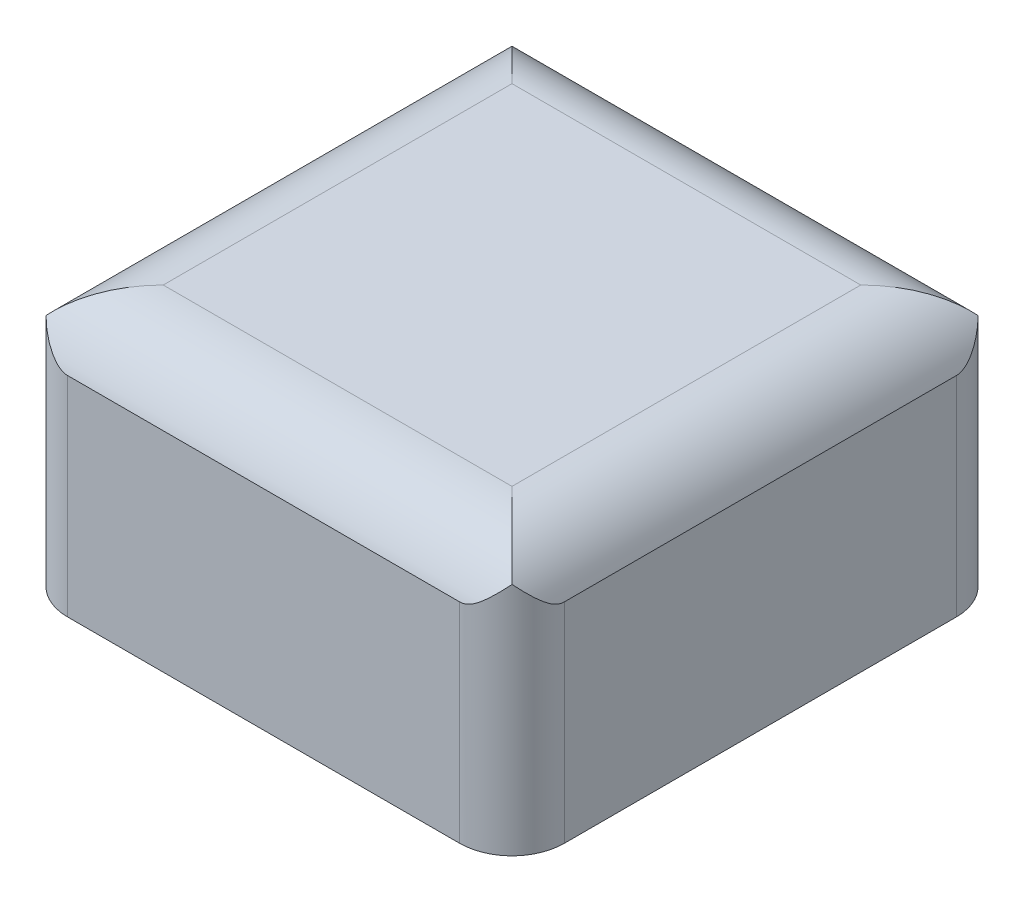
SolidWorks part; units mm, degrees
ref_plane "Front Plane" through (0, 0, 0) normal (0, 0, 1) x (1, 0, 0)
ref_plane "Top Plane" through (0, 0, 0) normal (0, 1, 0) x (1, 0, 0)
ref_plane "Right Plane" through (0, 0, 0) normal (1, 0, 0) x (0, 0, -1)
sketch "Sketch1" plane through (0, 0, 0) normal (0, 1, 0) x (1, 0, 0)
  line L1 (-2.5, 2.25) -> (2.5, 2.25)
  line L2 (-2.5, 2.25) -> (-2.5, -2.25)
  line L3 (-2.5, -2.25) -> (2.5, -2.25)
  line L4 (2.5, 2.25) -> (2.5, -2.25)
  line L5 (-2.5, 2.25) -> (2.5, -2.25) construction
  line L6 (-2.5, -2.25) -> (2.5, 2.25) construction
  line L7 (-0.7225, 2.065) -> (0.7225, 2.065)
  line L8 (-0.7225, 2.065) -> (-0.7225, -2.065)
  line L9 (-0.7225, -2.065) -> (0.7225, -2.065)
  line L10 (0.7225, 2.065) -> (0.7225, -2.065)
  line L11 (-0.7225, 2.065) -> (0.7225, -2.065) construction
  line L12 (-0.7225, -2.065) -> (0.7225, 2.065) construction
  line L13 (-2.065, 0.7225) -> (2.065, 0.7225)
  line L14 (-2.065, 0.7225) -> (-2.065, -0.7225)
  line L15 (-2.065, -0.7225) -> (2.065, -0.7225)
  line L16 (2.065, 0.7225) -> (2.065, -0.7225)
  line L17 (-2.065, 0.7225) -> (2.065, -0.7225) construction
  line L18 (-2.065, -0.7225) -> (2.065, 0.7225) construction
  point P0 (0, 0)
  point P6 (0, 0)
  point P11 (0, 0)
  dimension "D1" = 5
  dimension "D2" = 4.5
  dimension "D3" = 1.445
  dimension "D4" = 4.13
  dimension "D5" = 1.445
  dimension "D6" = 4.13
extrude "Boss-Extrude1" add sketch "Sketch1" along normal blind 4 contours L4 L1 L2 L3 L13 L16 L15 L10 L9 L8 L14 L7
sketch "Sketch2" plane through (0, 4, 0) normal (0, 1, 0) x (1, 0, 0)
  line L1 (-2.5, 2.25) -> (2.5, 2.25)
  line L2 (-2.5, 2.25) -> (-2.5, -2.25)
  line L3 (-2.5, -2.25) -> (2.5, -2.25)
  line L4 (2.5, 2.25) -> (2.5, -2.25)
  line L5 (-2.5, 2.25) -> (2.5, -2.25) construction
  line L6 (-2.5, -2.25) -> (2.5, 2.25) construction
  point P0 (0, 0)
extrude "Boss-Extrude2" add sketch "Sketch2" along normal blind 2
sketch "Sketch3" plane through (0, 6, 0) normal (0, 1, 0) x (1, 0, 0)
  line L1 (-9.5, 9.5) -> (9.5, 9.5)
  line L2 (-9.5, 9.5) -> (-9.5, -9.5)
  line L3 (-9.5, -9.5) -> (9.5, -9.5)
  line L4 (9.5, 9.5) -> (9.5, -9.5)
  line L5 (-9.5, 9.5) -> (9.5, -9.5) construction
  line L6 (-9.5, -9.5) -> (9.5, 9.5) construction
  point P0 (0, 0)
  dimension "D1" = 19
  dimension "D2" = 19
extrude "Boss-Extrude3" add sketch "Sketch3" along normal blind 2
fillet "Fillet1" radius 3 4 edges at (0, 8, 9.5) (-9.5, 8, 0) (0, 8, -9.5) (9.5, 8, 0)
sketch "Sketch4" plane through (0, 6, 0) normal (0, -1, 0) x (1, 0, 0)
  line L1 (-9.5, 9.5) -> (-8, 9.5)
  line L2 (-9.5, 9.5) -> (-9.5, 8)
  line L3 (-9.5, 8) -> (-8, 8)
  line L4 (-8, 9.5) -> (-8, 8)
  line L5 (-9.5, 9.5) -> (-8, 8) construction
  line L6 (-9.5, 8) -> (-8, 9.5) construction
  line L7 (9.5, -9.5) -> (8, -9.5)
  line L8 (9.5, -9.5) -> (9.5, -8)
  line L9 (9.5, -8) -> (8, -8)
  line L10 (8, -9.5) -> (8, -8)
  line L11 (9.5, -9.5) -> (8, -8) construction
  line L12 (9.5, -8) -> (8, -9.5) construction
  line L13 (-9.5, 9.5) -> (9.5, 9.5)
  line L14 (-9.5, 9.5) -> (-9.5, -9.5)
  line L15 (-9.5, -9.5) -> (9.5, -9.5)
  line L16 (9.5, 9.5) -> (9.5, -9.5)
  line L17 (-9.5, 9.5) -> (9.5, -9.5) construction
  line L18 (-9.5, -9.5) -> (9.5, 9.5) construction
  line L19 (8, -8) -> (-8, -8)
  line L20 (8, -8) -> (8, 8)
  line L21 (8, 8) -> (-8, 8)
  line L22 (-8, -8) -> (-8, 8)
  line L23 (8, -8) -> (-8, 8) construction
  line L24 (8, 8) -> (-8, -8) construction
  point P4 (-8.75, 8.75)
  point P10 (8.75, -8.75)
  point P12 (0, 0)
  point P13 (0, 0)
  line M9 (9.5, -9.5) -> (9.5, 9.5)
  line M10 (9.5, 9.5) -> (-9.5, 9.5)
  line M11 (-9.5, 9.5) -> (-9.5, -9.5)
  line M12 (-9.5, -9.5) -> (9.5, -9.5)
  dimension "D1" = 1.5
  dimension "D2" = 1.5
  dimension "D3" = 1.5
extrude "Boss-Extrude4" add sketch "Sketch4" along normal blind 8 contours L19 L22 L3 L10 M11 M12 | L21 L20 L9 L4 M9 M10 | L10 L9 M12 M9 | L4 L3 M10 M11
fillet "Fillet3" radius 3 4 edges at (0, 6, -2.25) (-2.5, 6, 0) (0, 6, 2.25) (2.5, 6, 0)
fillet "Fillet4" radius 1 8 edges at (3.3787, 5.1213, 3.1287) (-3.3787, 5.1213, 3.1287) (-3.3787, 5.1213, -3.1287) (3.3787, 5.1213, -3.1287) (2.5, 1.5, 2.25) (-2.5, 1.5, 2.25) (-2.5, 1.5, -2.25) (2.5, 1.5, -2.25)
fillet "Fillet5" radius 2 8 edges at (-8, 6, 0) (0, 6, 8) (8, 6, 0) (0, 6, -8) (8, 2, -8) (-8, 2, -8) (-8, 2, 8) (8, 2, 8)
fillet "Fillet8" radius 2 4 edges at (-9.5, 2, 9.5) (9.5, 2, 9.5) (-9.5, 2, -9.5) (9.5, 2, -9.5)
fillet "Fillet9" radius 1 8 edges at (7.4142, -2, -7.4142) (8, -2, 0) (7.4142, -2, 7.4142) (0, -2, 8) (-7.4142, -2, 7.4142) (-8, -2, 0) (-7.4142, -2, -7.4142) (0, -2, -8)
